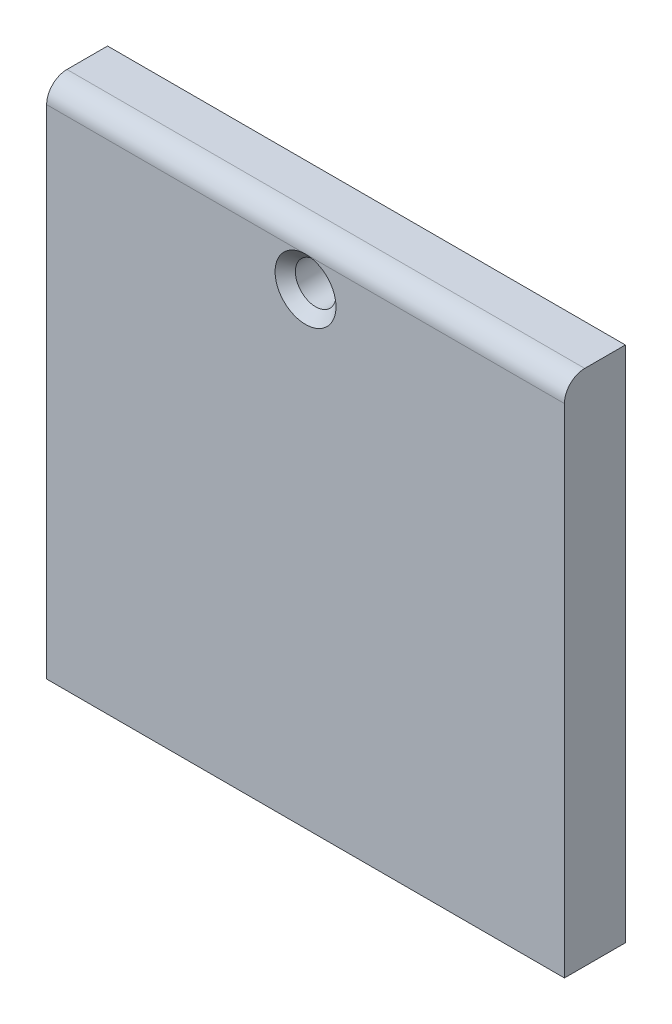
SolidWorks part; units mm, degrees
material "ABS"
ref_plane "Plano frontal" through (0, 0, 0) normal (0, 0, 1) x (1, 0, 0)
ref_plane "Plano superior" through (0, 0, 0) normal (0, 1, 0) x (1, 0, 0)
ref_plane "Plano direito" through (0, 0, 0) normal (1, 0, 0) x (0, 0, -1)
sketch "Esboço1" plane through (0, 0, 0) normal (0, 0, 1) x (1, 0, 0)
  line L1 (25.5, 25.5) -> (-25.5, 25.5)
  line L2 (25.5, 25.5) -> (25.5, -25.5)
  line L3 (25.5, -25.5) -> (-25.5, -25.5)
  line L4 (-25.5, 25.5) -> (-25.5, -25.5)
  line L5 (25.5, 25.5) -> (-25.5, -25.5) construction
  line L6 (25.5, -25.5) -> (-25.5, 25.5) construction
  point P0 (0, 0)
  dimension "D1" = 51
  dimension "D2" = 51
extrude "Ressalto-extrusão1" add sketch "Esboço1" along normal blind 6
sketch "Esboço2" plane through (0, 0, 0) normal (0, 0, -1) x (-1, 0, 0)
  line L0 (25.5, -25.5) -> (-25.5, -25.5) construction
  line L1 (-18.25, -16) -> (18.25, -16)
  line L2 (-18.25, -16) -> (-18.25, -22.5)
  line L3 (-18.25, -22.5) -> (18.25, -22.5)
  line L4 (18.25, -16) -> (18.25, -22.5)
  point P6 (0, -16)
  dimension "D1" = 36.5
  dimension "D2" = 6.5
  dimension "D3" = 3
extrude "Corte-extrusão1" cut sketch "Esboço2" against normal blind 4.5
sketch "Esboço3" plane through (0, 0, 6) normal (0, 0, 1) x (1, 0, 0)
  line L0 (25.5, 25.5) -> (-25.5, 25.5) construction
  circle A1 centre (0, 20.5) radius 2
  dimension "D1" = 4
  dimension "D2" = 5
extrude "Corte-extrusão2" cut sketch "Esboço3" against normal through all
sketch "Esboço4" plane through (0, 0, 0) normal (0, 0, -1) x (-1, 0, 0)
  line L0 (18.25, -16) -> (-18.25, -16) construction
  line L1 (-22, 16.5) -> (22, 16.5)
  line L2 (-22, 16.5) -> (-22, -14)
  line L3 (-22, -14) -> (22, -14)
  line L4 (22, 16.5) -> (22, -14)
  line L5 (-25.5, 25.5) -> (25.5, 25.5) construction
  point P4 (22, 17.2625)
  point P5 (0, 16.5)
  point P6 (-22, 16.7072)
  dimension "D1" = 9
  dimension "D2" = 2
  dimension "D3" = 44
extrude "Corte-extrusão3" cut sketch "Esboço4" against normal up to surface (4.5 mm away) up to face at (0, -19.25, 4.5)
fillet "Filete1" radius 2 1 edges at (0, 25.5, 6)
chamfer "Chanfro1" distance 1 angle 45 1 edges at (2, 20.5, 6)
sketch "Esboço5" plane through (0, 0, 0) normal (0, 0, -1) x (-1, 0, 0)
  line L0 (-25.5, -25.5) -> (-25.5, 25.5) construction
  line L1 (-23.5, 19.5) -> (-21.5, 19.5)
  line L2 (-23.5, 19.5) -> (-23.5, 23.5)
  line L3 (-23.5, 23.5) -> (-19.5, 23.5)
  line L4 (-19.5, 21.5) -> (-19.5, 23.5)
  line L5 (21.5, 19.5) -> (23.5, 19.5)
  line L6 (19.5, 21.5) -> (19.5, 23.5)
  line L7 (19.5, 23.5) -> (23.5, 23.5)
  line L8 (23.5, 19.5) -> (23.5, 23.5)
  line L11 (19.5, 21.5) -> (21.5, 21.5)
  line L12 (21.5, 19.5) -> (21.5, 21.5)
  line L15 (-19.5, 21.5) -> (-21.5, 21.5)
  line L16 (-21.5, 19.5) -> (-21.5, 21.5)
  line L17 (-25.5, 25.5) -> (25.5, 25.5) construction
  line L18 (25.5, 25.5) -> (25.5, -25.5) construction
  point P22 (-23.5, 21.5)
  point P24 (-21.5, 23.5)
  dimension "D1" = 2
  dimension "D2" = 2
  dimension "D3" = 4
  dimension "D4" = 2
  dimension "D5" = 4
extrude "Ressalto-extrusão2" add sketch "Esboço5" along normal blind 2
sketch "Esboço6" plane through (-22, 0, 0) normal (1, 0, 0) x (0, 0, -1)
  line L0 (0, -16) -> (2, -14)
  line L1 (2, -14) -> (0, -14)
  line L2 (-4.5, -1.5) -> (2, -1.5)
  line L3 (-4.5, 16.5) -> (-4.5, -14) construction
  line L4 (2, -1.5) -> (-4.5, -4)
  line L5 (0, -14) -> (0, 16.5) construction
  line L6 (-4.5, 8.5) -> (2, 11)
  line L7 (2, 11) -> (-4.5, 11)
  line L8 (-4.5, 11) -> (-4.5, 8.5)
  line L9 (-4.5, -1.5) -> (-4.5, -4)
  line L10 (0, -14) -> (0, -16)
  dimension "D1" = 2
  dimension "D2" = 2
  dimension "D3" = 2
  dimension "D4" = 12.5
  dimension "D5" = 12.5
  dimension "D6" = 2.5
extrude "Ressalto-extrusão3" add sketch "Esboço6" along normal up to surface (44 mm away) up to face at (22, 1.25, 2.25)
equation "\"D5@Esboço6\"=\"D4@Esboço6\""
